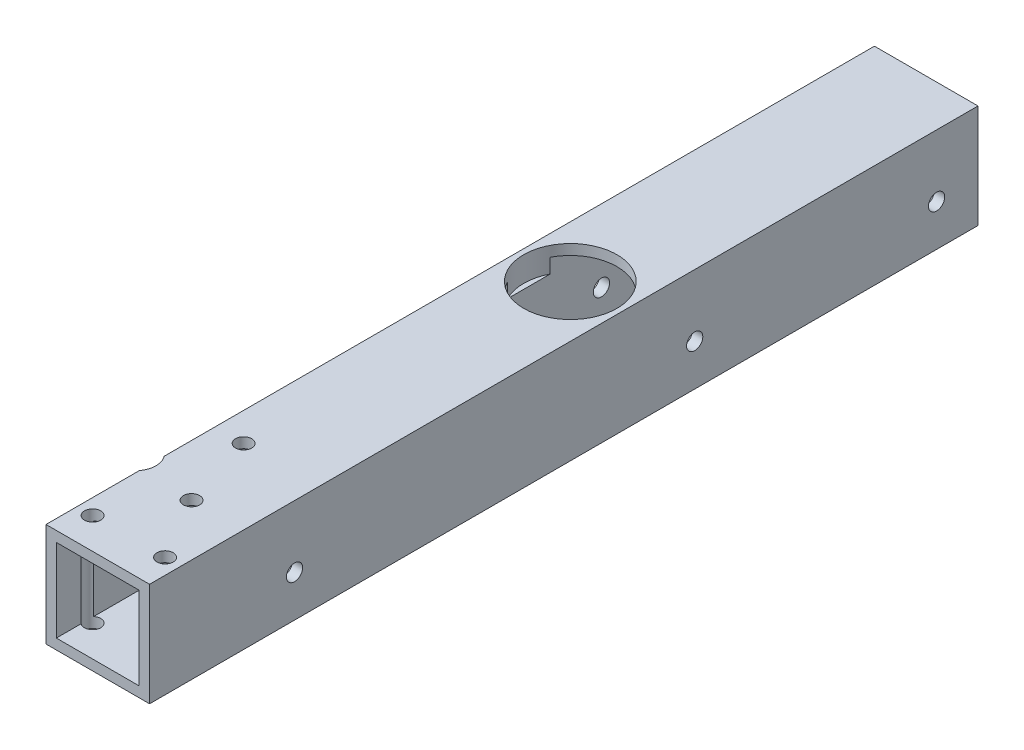
SolidWorks part; units mm, degrees
material "6061 Alloy"
ref_plane "Front Plane" through (0, 0, 0) normal (0, 0, 1) x (1, 0, 0)
ref_plane "Top Plane" through (0, 0, 0) normal (0, 1, 0) x (1, 0, 0)
ref_plane "Right Plane" through (0, 0, 0) normal (1, 0, 0) x (0, 0, -1)
sketch "Sketch1" plane through (0, 0, 0) normal (0, 0, 1) x (1, 0, 0)
  line L0 (-12.7, 12.7) -> (12.7, 12.7)
  line L2 (-15.875, 15.875) -> (15.875, 15.875)
  line L3 (-15.875, 15.875) -> (-15.875, -15.875)
  line L4 (-15.875, -15.875) -> (15.875, -15.875)
  line L5 (15.875, 15.875) -> (15.875, -15.875)
  line L10 (12.7, 12.7) -> (12.7, -12.7)
  line L11 (-12.7, -12.7) -> (12.7, -12.7)
  line L12 (-12.7, 12.7) -> (-12.7, -12.7)
  point P12 (0, 15.875)
  point P14 (15.875, 0)
  dimension "Wall Thickness" = 3.175
  dimension "Outside Width" = 31.75
  dimension "Outside Height" = 31.75
  dimension "Inside Height" = 25.4
  dimension "Inside Width" = 25.4
sketch "Sketch2" plane through (0, 0, 0) normal (1, 0, 0) x (0, 0, -1)
  line L0 (127, 0) -> (-127, 0)
  point P4 (0, 0)
  point P7 (-127, 0)
  point P10 (127, 0)
  dimension "Length" = 254
sketch "Sketch3" plane through (0, 0, 0) normal (0, 0, 1) x (1, 0, 0)
  line L21 (15.875, 15.875) -> (-15.875, 15.875)
  line L22 (15.875, -15.875) -> (15.875, 15.875)
  line L23 (-15.875, -15.875) -> (15.875, -15.875)
  line L24 (-15.875, 15.875) -> (-15.875, -15.875)
  line L25 (15.875, 15.875) -> (-15.875, 15.875)
  line L26 (15.875, -15.875) -> (15.875, 15.875)
  line L27 (-15.875, -15.875) -> (15.875, -15.875)
  line L28 (-15.875, 15.875) -> (-15.875, -15.875)
  line L29 (12.7, 12.7) -> (-12.7, 12.7)
  line L30 (12.7, -12.7) -> (12.7, 12.7)
  line L31 (-12.7, -12.7) -> (12.7, -12.7)
  line L32 (-12.7, 12.7) -> (-12.7, -12.7)
  line L33 (12.7, 12.7) -> (-12.7, 12.7)
  line L34 (12.7, -12.7) -> (12.7, 12.7)
  line L35 (-12.7, -12.7) -> (12.7, -12.7)
  line L36 (-12.7, 12.7) -> (-12.7, -12.7)
  dimension "D1" = 0
  dimension "D2" = 0
extrude "Boss-Extrude1" add sketch "Sketch3" along normal up to vertex (127 mm away) and the other way up to vertex (127 mm away) up to point (0, 0, 127) other way up to point (0, 0, -127)
sketch "Drawing Reference" plane through (0, 0, 0) normal (1, 0, 0) x (0, 0, -1)
  line L0 (-127, 0) -> (127, 0) construction
  line L1 (0, -15.875) -> (0, 15.875) construction
  line L2 (-127, -15.875) -> (127, -15.875) construction
  line L5 (-127, 15.875) -> (127, 15.875) construction
  point P7 (-104.14, 0)
  point P8 (104.14, 0)
  dimension "D1" = 22.86
sketch "Sketch4" plane through (0, 15.875, 0) normal (0, 1, 0) x (1, 0, 0)
  line L0 (0, -127) -> (0, -117.475) construction
  line L1 (15.875, -127) -> (-15.875, -127) construction
  line L2 (0, -117.475) -> (11.1125, -117.475) construction
  line L3 (0, -117.475) -> (-11.1125, -117.475) construction
  line L4 (0, -117.475) -> (0, 17.8816) construction
  line L5 (0, -117.475) -> (0, -98.2472) construction
  point P5 (-7.1119, -75.1713)
  dimension "D1" = 135.3566
  dimension "D2" = 22.225
  dimension "D3" = 9.525
hole_wizard "#10 Clearance Hole1" positions "Sketch5" profile "Sketch6" hole size "#10" standard "ANSI Inch" end condition through all
sketch "Sketch5" plane through (0, 15.875, 0) normal (0, 1, 0) x (1, 0, 0)
  point P0 (-11.1125, -117.475)
  point P3 (11.1125, -117.475)
  point P7 (0, -98.2472)
  point P10 (-7.1119, -75.1713)
sketch "Sketch6" plane through (-11.1125, 15.875, 117.475) normal (1, 0, 0) x (0, 0, 1)
  line L0 (0, 0) -> (0, 31.75)
  line L1 (0, 31.75) -> (2.4892, 31.75)
  line L2 (2.4892, 31.75) -> (2.4892, 0)
  line L5 (2.4892, 0) -> (0, 0)
  line L11 (0, -6.35) -> (0, 107.95) construction
  dimension "Thru Hole Dia." = 4.9784
  dimension "Thru Hole Depth" = 31.75
sketch "Sketch7" plane through (0, 15.875, 0) normal (0, 1, 0) x (1, 0, 0)
  circle A0 centre (0, 17.8816) radius 14.2875
  dimension "D1" = 28.575
extrude "Cut-Extrude1" cut sketch "Sketch7" against normal blind 7.62
sketch "Sketch8" plane through (0, -15.875, 0) normal (0, -1, 0) x (1, 0, 0)
  circle A0 centre (0, -17.8816) radius 14.2875
  dimension "D1" = 28.575
extrude "Cut-Extrude2" cut sketch "Sketch8" against normal blind 7.62
sketch "Sketch9" plane through (15.875, 0, 0) normal (1, 0, 0) x (0, 0, -1)
  line L0 (-127, -3.175) -> (-82.55, -3.175) construction
  line L2 (-82.55, -3.175) -> (114.3, -3.175) construction
  line L3 (-127, 15.875) -> (-127, -3.175) construction
  line L4 (52.832, -3.175) -> (40.132, -3.175) construction
  line L5 (52.832, 10.4775) -> (52.832, -434.0225) construction
  dimension "D1" = 44.45
  dimension "D2" = 19.05
  dimension "D3" = 12.7
hole_wizard "#10 Clearance Hole2" positions "Sketch10" profile "Sketch11" hole size "#10" standard "ANSI Inch" end condition through all
sketch "Sketch10" plane through (15.875, 0, 0) normal (1, 0, 0) x (0, 0, -1)
  point P0 (-82.55, -3.175)
  point P4 (114.3, -3.175)
  point P8 (40.132, -3.175)
sketch "Sketch11" plane through (15.875, -3.175, 82.55) normal (0, 1, 0) x (0, 0, -1)
  line L0 (0, 0) -> (0, 31.75)
  line L1 (0, 31.75) -> (2.4892, 31.75)
  line L2 (2.4892, 31.75) -> (2.4892, 0)
  line L5 (2.4892, 0) -> (0, 0)
  line L11 (0, -6.35) -> (0, 107.95) construction
  dimension "Thru Hole Dia." = 4.9784
  dimension "Thru Hole Depth" = 31.75
sketch "Sketch12" plane through (0, 15.875, 0) normal (0, 1, 0) x (1, 0, 0)
  line L0 (-20.955, -94.5576) -> (-15.875, -94.5576) construction
  line L1 (-15.875, -127) -> (-15.875, 127) construction
  circle A0 centre (-20.955, -94.5576) radius 6.35
  dimension "D1" = 5.08
extrude "Cut-Extrude3" cut sketch "Sketch12" against normal through all
sketch "Sketch13" plane through (0, -15.875, 0) normal (0, -1, 0) x (1, 0, 0)
  line L0 (0, 0.1524) -> (0, -35.9156) construction
  line L1 (0, -17.8816) -> (3.2229, -17.8816) construction
  point P8 (0, -17.8816)
  dimension "D1" = 36.068
hole_wizard "Tap Drill for #10-32 Tap1" positions "Sketch14" profile "Sketch15" hole size "#10-32" standard "ANSI Inch"
sketch "Sketch14" plane through (0, -15.875, 0) normal (0, -1, 0) x (-1, 0, 0)
  point P2 (0, 35.9156)
  point P5 (0, -0.1524)
  point P9 (0, 0)
sketch "Sketch15" plane through (0, -15.875, -35.9156) normal (1, 0, 0) x (0, 0, -1)
  line L0 (0, 0) -> (0, 6.2933)
  line L1 (0, 6.2933) -> (2.0193, 5.08)
  line L2 (2.0193, 5.08) -> (2.0193, 0)
  line L5 (2.0193, 0) -> (0, 0)
  line L10 (0, 6.2933) -> (-2.0193, 5.08) construction
  line L11 (0, -6.35) -> (0, 107.95) construction
  dimension "Hole Dia." = 4.0386
  dimension "Hole Depth" = 5.08
  dimension "Drill Angle" = 118
equation "\"D1@Drawing Reference\"=\"Outside Width@Sketch1\" * 0.72"
